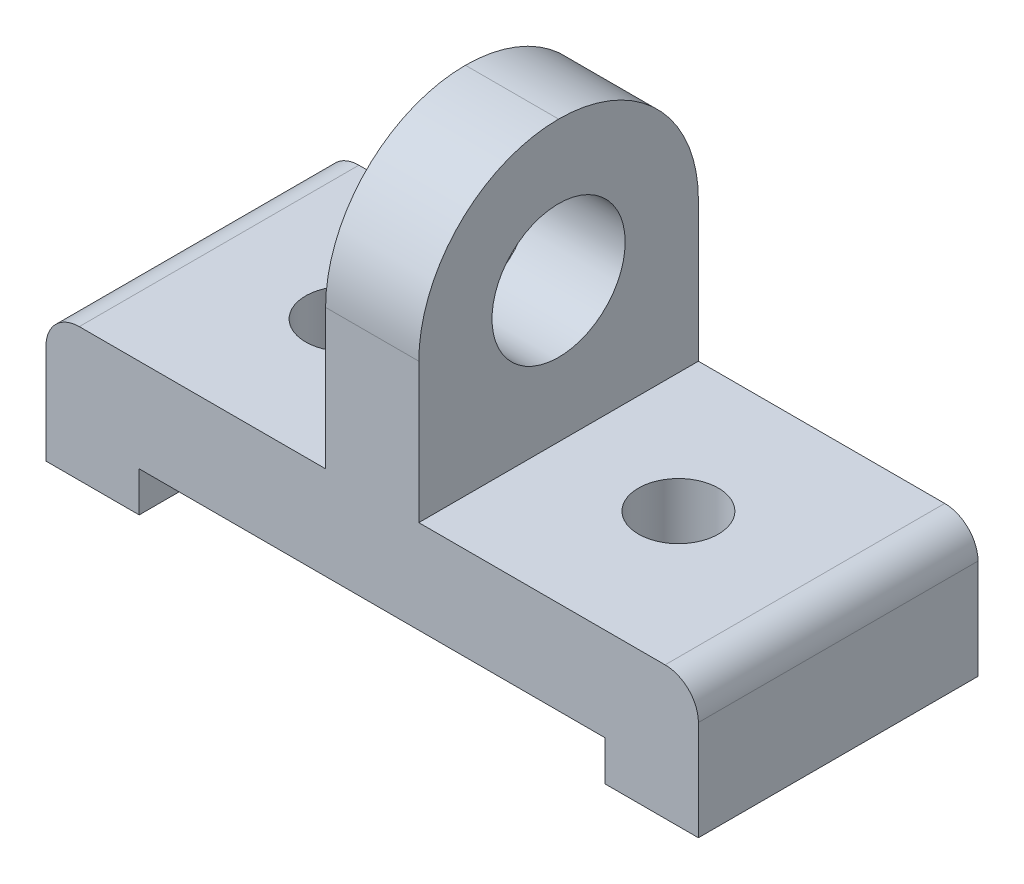
SolidWorks part; units mm, degrees
ref_plane "Front Plane" through (0, 0, 0) normal (0, 0, 1) x (1, 0, 0)
ref_plane "Top Plane" through (0, 0, 0) normal (0, 1, 0) x (1, 0, 0)
ref_plane "Right Plane" through (0, 0, 0) normal (1, 0, 0) x (0, 0, -1)
sketch "Sketch1" plane through (0, 0, 0) normal (0, 1, 0) x (1, 0, 0)
  line L1 (-49, 21) -> (49, 21)
  line L2 (-49, 21) -> (-49, -21)
  line L3 (-49, -21) -> (49, -21)
  line L4 (49, 21) -> (49, -21)
  line L5 (-49, 21) -> (49, -21) construction
  line L6 (-49, -21) -> (49, 21) construction
  point P0 (0, 0)
  dimension "D1" = 98
  dimension "D2" = 42
extrude "Boss-Extrude1" add sketch "Sketch1" along normal blind 20
sketch "Sketch2" plane through (0, 0, 21) normal (0, 0, 1) x (1, 0, 0)
  line L0 (-49, 0) -> (49, 0) construction
  line L1 (-35, 0) -> (35, 0)
  line L2 (-35, 0) -> (-35, 6)
  line L3 (-35, 6) -> (35, 6)
  line L4 (35, 0) -> (35, 6)
  line L5 (-49, 20) -> (-49, 0) construction
  line L6 (49, 20) -> (49, 0) construction
  dimension "D1" = 14
  dimension "D2" = 14
  dimension "D3" = 6
extrude "Cut-Extrude1" cut sketch "Sketch2" against normal through all both and the other way through all
sketch "Sketch3" plane through (0, 20, 0) normal (0, 1, 0) x (1, 0, 0)
  line L0 (-49, -21) -> (49, -21) construction
  line L1 (-7, 21) -> (7, 21)
  line L2 (-7, 21) -> (-7, -21)
  line L3 (-7, -21) -> (7, -21)
  line L4 (7, 21) -> (7, -21)
  line L5 (-7, 21) -> (7, -21) construction
  line L6 (-7, -21) -> (7, 21) construction
  point P0 (0, 0)
  dimension "D1" = 14
extrude "Boss-Extrude2" add sketch "Sketch3" along normal blind 42
fillet "Fillet1" radius 21 2 edges at (0, 62, -21) (0, 62, 21)
sketch "Sketch4" plane through (7, 0, 0) normal (1, 0, 0) x (0, 0, -1)
  circle A0 centre (0, 41) radius 10
  dimension "D1" = 20
extrude "Cut-Extrude2" cut sketch "Sketch4" against normal through all both and the other way through all
sketch "Sketch5" plane through (0, 20, 0) normal (0, 1, 0) x (1, 0, 0)
  line L0 (0, 0) -> (40.6553, 0) construction
  line L2 (25, 13.1566) -> (25, -14.6541) construction
  line L3 (49, -21) -> (49, 21) construction
  circle A0 centre (25, 0) radius 6
  dimension "D1" = 12
  dimension "D2" = 24
extrude "Cut-Extrude4" cut sketch "Sketch5" against normal through all contours A0
mirror "Mirror2" about plane through (0, 0, 0) normal (1, 0, 0) of "Cut-Extrude4"
fillet "Fillet3" radius 5 2 edges at (-49, 20, 0) (49, 20, 0)
